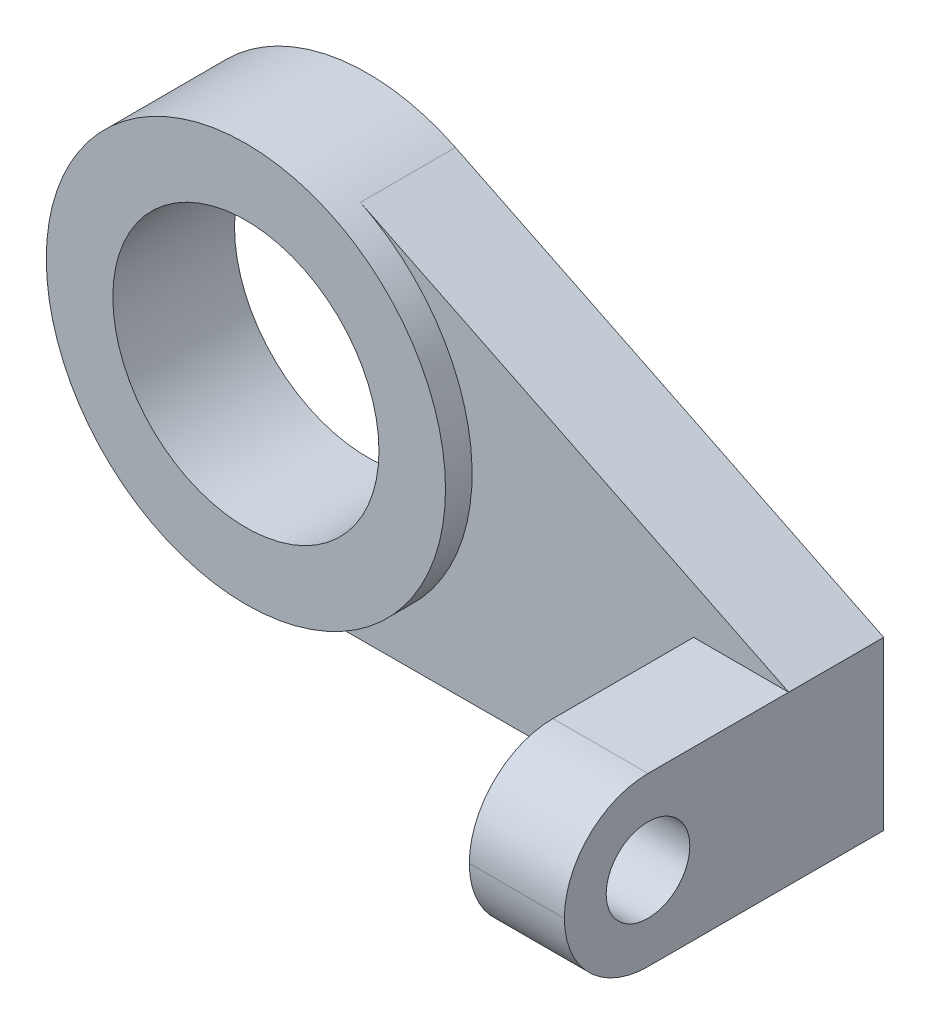
SolidWorks part; units mm, degrees
ref_plane "정면" through (0, 0, 0) normal (0, 0, 1) x (1, 0, 0)
ref_plane "윗면" through (0, 0, 0) normal (0, 1, 0) x (1, 0, 0)
ref_plane "우측면" through (0, 0, 0) normal (1, 0, 0) x (0, 0, -1)
sketch "스케치1" plane through (0, 0, 0) normal (0, 0, 1) x (1, 0, 0)
  circle A0 centre (0, 0) radius 52.5
  circle A1 centre (0, 0) radius 35
  dimension "D1" = 70
  dimension "D2" = 105
extrude "보스-돌출1" add sketch "스케치1" along normal blind 32
sketch "스케치2" plane through (0, 0, 0) normal (0, 0, -1) x (-1, 0, 0)
  line L0 (-23.122, 47.1341) -> (-135.759, -8.1209)
  line L1 (-135.759, -8.1209) -> (-135.759, -52.1209)
  line L2 (-135.759, -52.1209) -> (-0.1467, -52.4998)
  circle A0 centre (0, 0) radius 52.5 construction
  circle A2 centre (0, 0) radius 52.5
  arc A3 (-23.122, 47.1341) -> (-0.1467, -52.4998) centre (0, 0) ccw
  dimension "D1" = 44
  dimension "D2" = 0
extrude "보스-돌출3" add sketch "스케치2" against normal blind 25 contours L0 L1 L2 A3
sketch "스케치3" plane through (0, 0, 25) normal (0, 0, 1) x (1, 0, 0)
  line L1 (135.759, -52.1209) -> (110.759, -52.1209)
  line L2 (135.759, -52.1209) -> (135.759, -8.1209)
  line L3 (135.759, -8.1209) -> (110.759, -8.1209)
  line L4 (110.759, -52.1209) -> (110.759, -8.1209)
  point P5 (123.259, -52.1209)
  dimension "D1" = 44
  dimension "D2" = 25
extrude "보스-돌출4" add sketch "스케치3" along normal blind 59
fillet "필렛1" radius 22 2 edges at (123.259, -8.1209, 84) (123.259, -52.1209, 84)
sketch "스케치4" plane through (110.759, 0, 0) normal (-1, 0, 0) x (0, 0, 1)
  circle A0 centre (62, -30.1209) radius 11
  dimension "D1" = 22
extrude "컷-돌출1" cut sketch "스케치4" against normal blind 59
